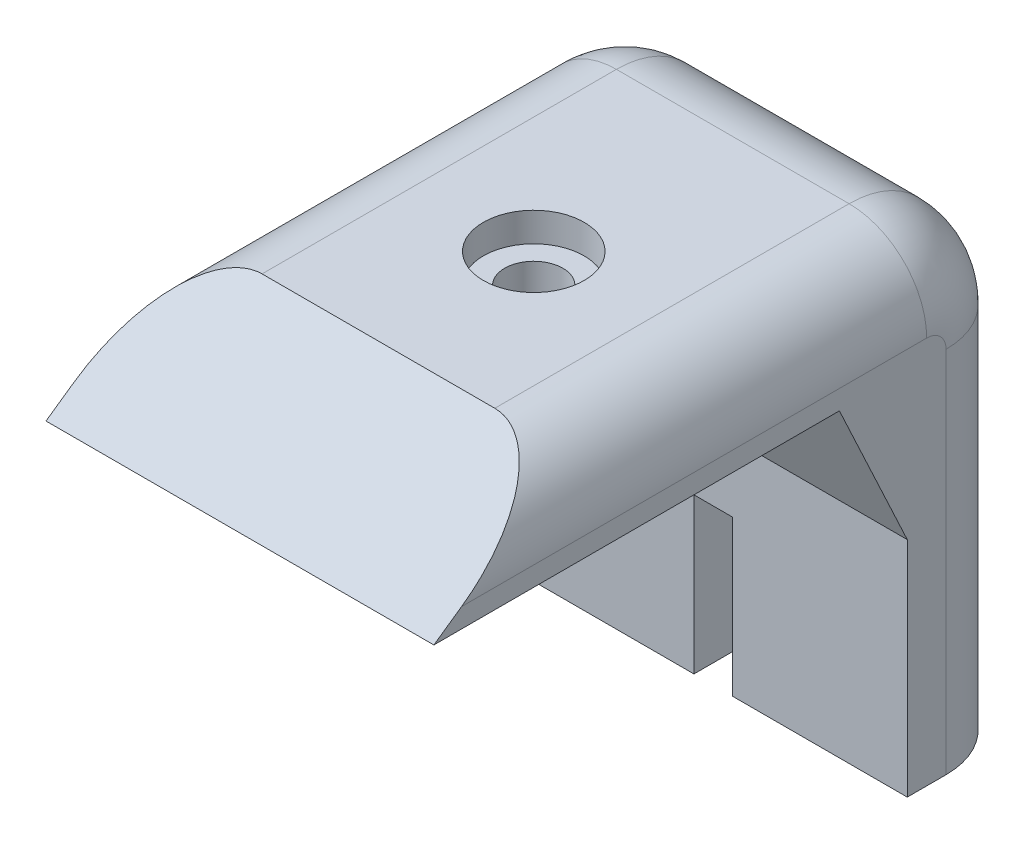
SolidWorks part; units mm, degrees
ref_plane "Front Plane" through (0, 0, 0) normal (0, 0, 1) x (1, 0, 0)
ref_plane "Top Plane" through (0, 0, 0) normal (0, 1, 0) x (1, 0, 0)
ref_plane "Right Plane" through (0, 0, 0) normal (1, 0, 0) x (0, 0, -1)
sketch "Sketch1" plane through (0, 0, 0) normal (1, 0, 0) x (0, 0, -1)
  line L7 (0, 0) -> (7.1407, 5)
  line L8 (24.4101, 0) -> (24.4101, -11)
  line L10 (24.4101, 5) -> (25.4101, 5)
  line L11 (30.4101, 0) -> (30.4101, -11)
  line L12 (24.4101, -11) -> (30.4101, -11)
  line L13 (7.1407, 5) -> (24.4101, 5)
  line L14 (0, 0) -> (24.4101, 0)
  line L16 (24.2851, 0) -> (24.2851, -8) construction
  line L17 (24.2851, -32.5) -> (24.2851, -8) construction
  line L18 (24.2851, -8) -> (24.0351, -8) construction
  line L19 (24.4101, 0) -> (24.4101, 5) construction
  arc A0 (25.4101, 5) -> (30.4101, 0) centre (25.4101, 0) cw
  dimension "D6" = 1
  dimension "D7" = 6
  dimension "D1" = 5
  dimension "D2" = 0.25
  dimension "D3" = 16
  dimension "D4" = 35
extrude "Boss-Extrude1" add sketch "Sketch1" along normal blind 20
sketch "Sketch2" plane through (0, -11, 0) normal (0, -1, 0) x (1, 0, 0)
  line L0 (20, -24.4101) -> (0, -24.4101) construction
  line L1 (20, -30.4101) -> (11, -30.4101)
  line L2 (20, -30.4101) -> (20, -24.4101)
  line L3 (20, -24.4101) -> (11, -24.4101)
  line L4 (11, -30.4101) -> (11, -24.4101)
  line L5 (10, -30.4101) -> (10, -24.4101) construction
  line L6 (20, -30.4101) -> (0, -30.4101) construction
  line L7 (9, -30.4101) -> (9, -24.4101)
  line L8 (0, -24.4101) -> (9, -24.4101)
  line L9 (0, -30.4101) -> (0, -24.4101)
  line L10 (0, -30.4101) -> (9, -30.4101)
  dimension "D1" = 2
extrude "Boss-Extrude2" add sketch "Sketch2" along normal blind 8
chamfer "Chamfer1" distance 3.5 distance2 7.5 1 edges at (10, 0, -24.4101) first distance on face at (10, 0, -12.205)
sketch "Sketch3" plane through (0, 5, 0) normal (0, 1, 0) x (1, 0, 0)
  circle A0 centre (10, 15.1507) radius 1.25 construction
  circle A1 centre (10, 15.1507) radius 1.5
  circle A2 centre (10, 15.1507) radius 2.35 construction
  circle A3 centre (10, 15.1507) radius 2.6
  dimension "D2" = 0.25
  dimension "D1" = 2.5
  dimension "D3" = 4.7
  dimension "D4" = 0.25
extrude "Cut-Extrude1" cut sketch "Sketch3" against normal through all contours A1 region at (10, 5, -15.1507)
extrude "Cut-Extrude2" cut sketch "Sketch3<3>" against normal blind 1.5 contours A3 A1 region at (7.4735, 5, -15.1507)
sketch "Sketch3<3>" plane through (0, 5, 0) normal (0, 1, 0) x (1, 0, 0) same geometry as "Sketch3"
fillet "Fillet1" radius 4 6 edges at (0, 5, -16.2754) (0, 3.5355, -28.9456) (20, 5, -16.2754) (20, 3.5355, -28.9456) (0, -9.5, -30.4101) (20, -9.5, -30.4101)
equation "\"Tolerance\" = 0.25mm"
equation "\"Pocket_Head_M5\"= 8mm"
equation "\"Pocket_Head_M4\" = 7mm"
equation "\"Pocket_Nut_M4\" = 7mm"
equation "\"Pocket_Nut_M2.5\" = 5mm"
equation "\"Pocket_Nut_M5\"= 8mm"
equation "\"Pocket_Nut_M3\"= 5.5mm"
equation "\"Pocket_Head_M3\"= 5.5mm"
equation "\"Pocket_Head_M2.5\" = 4.7mm"
equation "\"Pocket_Head_M6\" = 10mm"
equation "\"D2@Sketch1\"=\"Tolerance\""
equation "\"D2@Sketch3\"=\"Tolerance\""
equation "\"D3@Sketch3\"=\"Pocket_Head_M2.5\""
equation "\"D4@Sketch3\"=\"Tolerance\""
